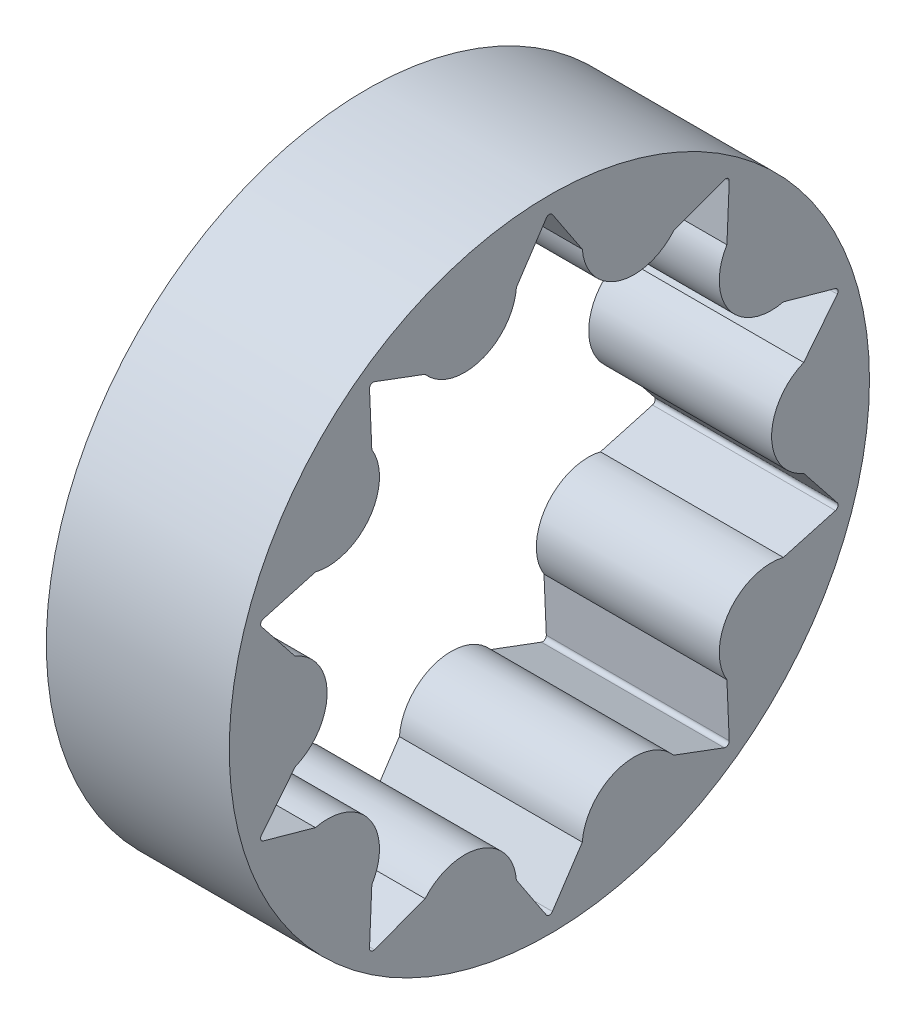
SolidWorks part; units mm, degrees
ref_plane "Front Plane" through (0, 0, 0) normal (0, 0, 1) x (1, 0, 0)
ref_plane "Top Plane" through (0, 0, 0) normal (0, 1, 0) x (1, 0, 0)
ref_plane "Right Plane" through (0, 0, 0) normal (1, 0, 0) x (0, 0, -1)
sketch "Sketch1" plane through (0, 0, 0) normal (1, 0, 0) x (0, 0, -1)
  line L0 (0, 0) -> (0, 16.75)
  line L1 (0, 0) -> (9.8454, 13.551)
  line L2 (0, 16.75) -> (1.8002, 14.035)
  line L3 (6.7932, 12.4127) -> (9.8454, 13.551)
  circle A0 centre (0, 0) radius 12.15
  circle A1 centre (0, 0) radius 16.75
  circle A2 centre (0, 0) radius 14.15 construction
  arc A3 (1.8002, 14.035) -> (6.7932, 12.4127) centre (4.6325, 14.2573) ccw
  dimension "D1" = 24.3
  dimension "D2" = 33.5
  dimension "D3" = 2.6
  dimension "D4" = 36
  dimension "D5" = 5.25
extrude "Boss-Extrude1" add sketch "Sketch1" along normal blind 5.3 contours L1 A0 L0 | A3 A0 L1 L3 | A3 L2 L0 A0 region at (0, 7.5775, -2.4621) region at (0, 13.656, -0.9718) region at (0, 11.6191, -7.2406)
pattern_circular "CirPattern1" count 10 over 360 about axis through (5.3, 0, 0) along (-1, 0, 0) of "Boss-Extrude1" reverse direction yes
fillet "Fillet1" radius 0.2 1 edges at (2.65, 16.75, 0)
fillet "Fillet3" radius 0.2 9 edges at (2.65, 13.551, 9.8454) (2.65, 5.176, 15.9302) (2.65, -5.176, 15.9302) (2.65, -13.551, 9.8454) (2.65, -16.75, 0) (2.65, -13.551, -9.8454) (2.65, -5.176, -15.9302) (2.65, 5.176, -15.9302) (2.65, 13.551, -9.8454)
sketch "Sketch2" plane through (0, 0, 0) normal (-1, 0, 0) x (0, 0, 1)
  circle A0 centre (0, 0) radius 10
  circle A1 centre (0, 0) radius 4.05
  dimension "D1" = 20
  dimension "D2" = 8.1
extrude "Boss-Extrude2" add sketch "Sketch2" along normal blind 16.7
extrude "Cut-Extrude1" cut sketch "Sketch2<2>" against normal through all both and the other way through all contours A1 region at (0, 0, 0)
sketch "Sketch2<2>" plane through (0, 0, 0) normal (-1, 0, 0) x (0, 0, 1) same geometry as "Sketch2"
sketch "Sketch3" plane through (5.3, 0, 0) normal (1, 0, 0) x (0, 0, -1)
  circle A0 centre (0, 0) radius 17.5
  circle M1 centre (0, 0) radius 4.05
  line M2 (-6.7932, 12.4127) -> (-9.5628, 13.4456)
  arc M3 (-9.5628, 13.4456) -> (-9.8325, 13.2497) centre (-9.6327, 13.2582) ccw
  line M4 (-9.8325, 13.2497) -> (-9.7059, 10.2965)
  arc M5 (-9.7059, 10.2965) -> (-12.7918, 6.0491) centre (-12.128, 8.8115) cw
  line M6 (-12.7918, 6.0491) -> (-15.6396, 5.2569)
  arc M7 (-15.6396, 5.2569) -> (-15.7426, 4.9398) centre (-15.586, 5.0642) ccw
  line M8 (-15.7426, 4.9398) -> (-13.9044, 2.625)
  arc M9 (-13.9044, 2.625) -> (-13.9044, -2.625) centre (-14.991, 0) cw
  line M10 (-13.9044, -2.625) -> (-15.7426, -4.9398)
  arc M11 (-15.7426, -4.9398) -> (-15.6396, -5.2569) centre (-15.586, -5.0642) ccw
  line M12 (-15.6396, -5.2569) -> (-12.7918, -6.0491)
  arc M13 (-12.7918, -6.0491) -> (-9.7059, -10.2965) centre (-12.128, -8.8115) cw
  line M14 (-9.7059, -10.2965) -> (-9.8325, -13.2497)
  arc M15 (-9.8325, -13.2497) -> (-9.5628, -13.4456) centre (-9.6327, -13.2582) ccw
  line M16 (-9.5628, -13.4456) -> (-6.7932, -12.4127)
  arc M17 (-6.7932, -12.4127) -> (-1.8002, -14.035) centre (-4.6325, -14.2573) cw
  line M18 (-1.8002, -14.035) -> (-0.1667, -16.4986)
  arc M19 (-0.1667, -16.4986) -> (0.1667, -16.4986) centre (0, -16.3881) ccw
  line M20 (0.1667, -16.4986) -> (1.8002, -14.035)
  arc M21 (1.8002, -14.035) -> (6.7932, -12.4127) centre (4.6325, -14.2573) cw
  line M22 (6.7932, -12.4127) -> (9.5628, -13.4456)
  arc M23 (9.5628, -13.4456) -> (9.8325, -13.2497) centre (9.6327, -13.2582) ccw
  line M24 (9.8325, -13.2497) -> (9.7059, -10.2965)
  arc M25 (9.7059, -10.2965) -> (12.7918, -6.0491) centre (12.128, -8.8115) cw
  line M26 (12.7918, -6.0491) -> (15.6396, -5.2569)
  arc M27 (15.6396, -5.2569) -> (15.7426, -4.9398) centre (15.586, -5.0642) ccw
  line M28 (15.7426, -4.9398) -> (13.9044, -2.625)
  arc M29 (13.9044, -2.625) -> (13.9044, 2.625) centre (14.991, 0) cw
  line M30 (13.9044, 2.625) -> (15.7426, 4.9398)
  arc M31 (15.7426, 4.9398) -> (15.6396, 5.2569) centre (15.586, 5.0642) ccw
  line M32 (15.6396, 5.2569) -> (12.7918, 6.0491)
  arc M33 (12.7918, 6.0491) -> (9.7059, 10.2965) centre (12.128, 8.8115) cw
  line M34 (9.7059, 10.2965) -> (9.8325, 13.2497)
  arc M35 (9.8325, 13.2497) -> (9.5628, 13.4456) centre (9.6327, 13.2582) ccw
  line M36 (9.5628, 13.4456) -> (6.7932, 12.4127)
  arc M37 (6.7932, 12.4127) -> (1.8002, 14.035) centre (4.6325, 14.2573) cw
  line M38 (1.8002, 14.035) -> (0.1667, 16.4986)
  arc M39 (0.1667, 16.4986) -> (-0.1667, 16.4986) centre (0, 16.3881) ccw
  line M40 (-0.1667, 16.4986) -> (-1.8002, 14.035)
  arc M41 (-1.8002, 14.035) -> (-6.7932, 12.4127) centre (-4.6325, 14.2573) cw
  dimension "D1" = 35
extrude "Boss-Extrude3" add sketch "Sketch3" along normal blind 10 separate body contours M41 M2 M3 M4 M5 M6 M7 M8 M9 M10 M11 M12 M13 M14 M15 M16 M17 M18 M19 M20 M21 M22 M23 M24 M25 M26 M27 M28 M29 M30 M31 M32 M33 M34 M35 M36 M37 M38 M39 M40 M1 | A0 region at (5.3, 11.1198, 3.613)
extrude "Cut-Extrude2" cut sketch "Sketch3<3>" against normal through all
sketch "Sketch3<3>" plane through (5.3, 0, 0) normal (1, 0, 0) x (0, 0, -1) same geometry as "Sketch3"
